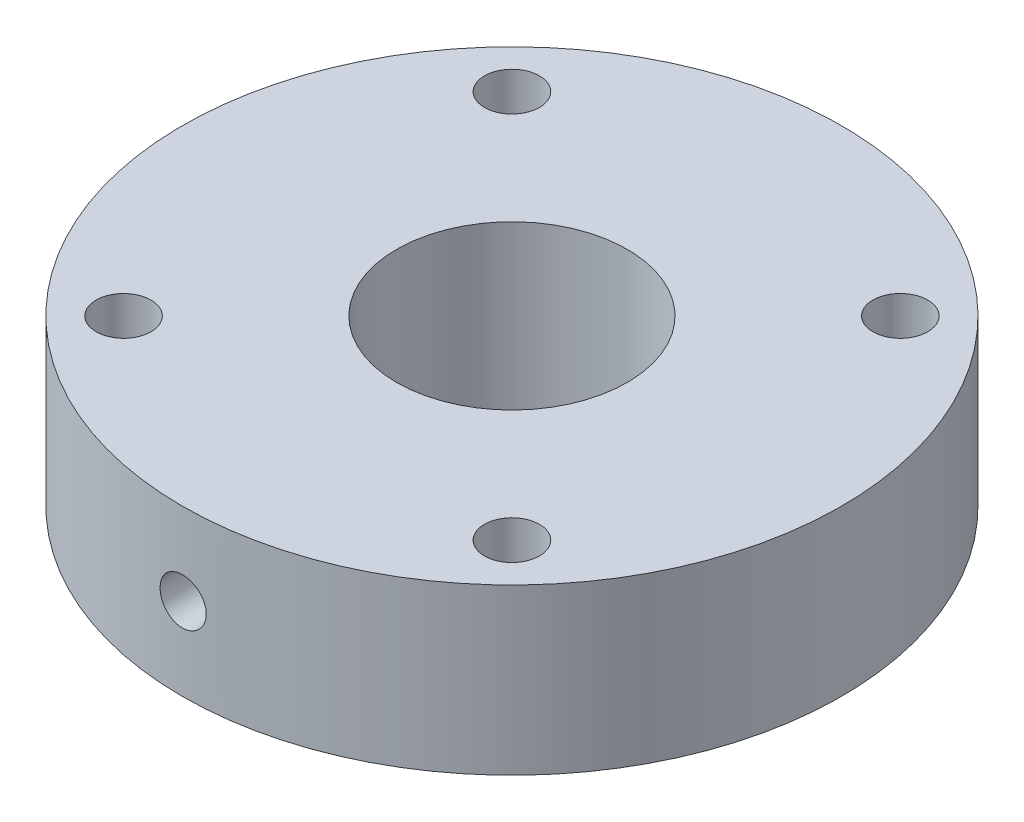
SolidWorks part; units mm, degrees
ref_plane "Front Plane" through (0, 0, 0) normal (0, 0, 1) x (1, 0, 0)
ref_plane "Top Plane" through (0, 0, 0) normal (0, 1, 0) x (1, 0, 0)
ref_plane "Right Plane" through (0, 0, 0) normal (1, 0, 0) x (0, 0, -1)
sketch "Sketch1" plane through (0, 0, 0) normal (0, 1, 0) x (1, 0, 0)
  line L0 (-17.6777, 17.6777) -> (17.6777, -17.6777) construction
  line L1 (0, 0) -> (-30, 0) construction
  line L2 (17.6777, 17.6777) -> (-17.6777, -17.6777) construction
  circle A0 centre (0, 0) radius 10.5
  circle A1 centre (0, 0) radius 14.2875 construction
  circle A2 centre (0, 0) radius 30
  circle A3 centre (0, 0) radius 25 construction
  circle A4 centre (17.6777, 17.6777) radius 2.5
  circle A5 centre (17.6777, -17.6777) radius 2.5
  circle A6 centre (-17.6777, -17.6777) radius 2.5
  circle A7 centre (-17.6777, 17.6777) radius 2.5
  dimension "D1" = 21
  dimension "D2" = 28.575
  dimension "D3" = 60
  dimension "D4" = 50
  dimension "D5" = 5
  dimension "D6" = 45
extrude "Boss-Extrude1" add sketch "Sketch1" along normal blind 7.5 and the other way blind 7.5
sketch "Sketch2" plane through (0, 0, 0) normal (0, 0, 1) x (1, 0, 0)
  circle A0 centre (0, 0) radius 2.1
  dimension "D1" = 4.2
extrude "Cut-Extrude2" cut sketch "Sketch2" along normal blind 10 from offset 20
